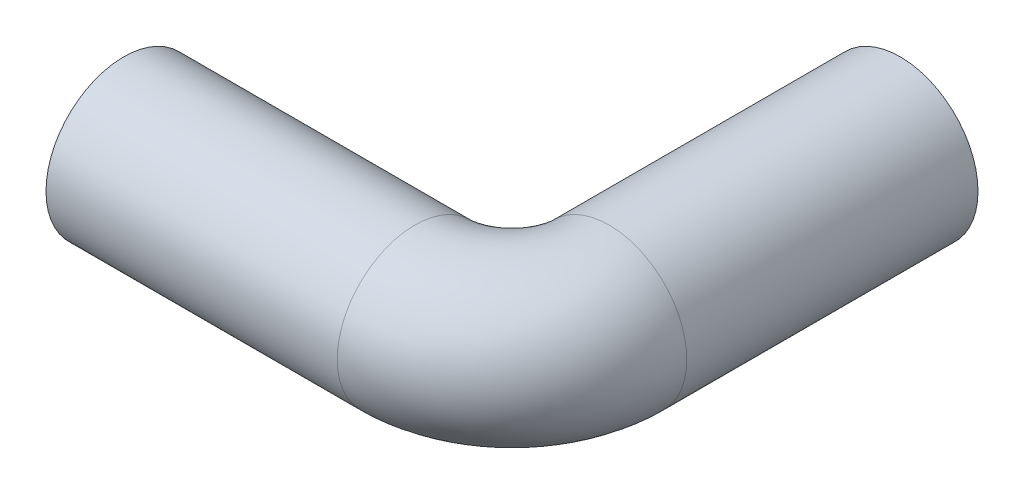
SolidWorks part; units mm, degrees
ref_plane "Front Plane" through (0, 0, 0) normal (0, 0, 1) x (1, 0, 0)
ref_plane "Top Plane" through (0, 0, 0) normal (0, 1, 0) x (1, 0, 0)
ref_plane "Right Plane" through (0, 0, 0) normal (1, 0, 0) x (0, 0, -1)
sketch "Sketch1" plane through (0, 0, 0) normal (0, 1, 0) x (1, 0, 0)
  line L0 (0, 0) -> (15, 0)
  line L1 (20, 5) -> (20, 20)
  arc A0 (15, 0) -> (20, 5) centre (15, 5) ccw
  point P6 (20, 0)
  dimension "D2" = 5
  dimension "D1" = 20
sweep "Sweep-Thin1" add path "Sketch1" circular profile diameter 8 parameters "D1"=0.5, "D3"=8
